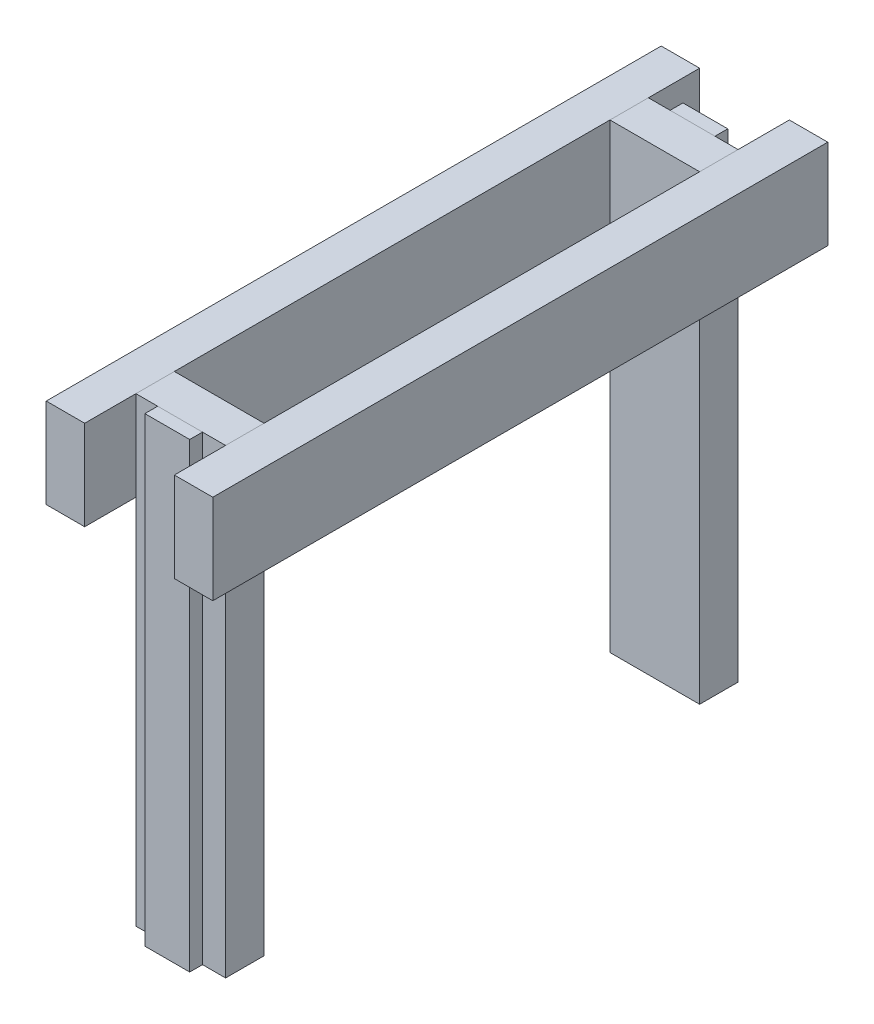
SolidWorks part; units mm, degrees
material "Oak"
ref_plane "Front Plane" through (0, 0, 0) normal (0, 0, 1) x (1, 0, 0)
ref_plane "Top Plane" through (0, 0, 0) normal (0, 1, 0) x (1, 0, 0)
ref_plane "Right Plane" through (0, 0, 0) normal (1, 0, 0) x (0, 0, -1)
sketch "Sketch3" plane through (0, 0, 0) normal (0, 1, 0) x (1, 0, 0)
  line L0 (0, 0) -> (0, -234.95) construction
  line L2 (-44.45, -254) -> (44.45, -254)
  line L3 (-44.45, -254) -> (-44.45, -215.9)
  line L4 (-44.45, -215.9) -> (44.45, -215.9)
  line L5 (44.45, -254) -> (44.45, -215.9)
  line L6 (-44.45, -254) -> (44.45, -215.9) construction
  line L7 (-44.45, -215.9) -> (44.45, -254) construction
  dimension "D1" = 38.1
  dimension "D2" = 88.9
  dimension "D3" = 254
extrude "Vertical Board" add sketch "Sketch3" against normal blind 457.2
mirror "Vertical Board Mirror" about plane through (0, 0, 0) normal (0, 0, 1) of bodies 107
sketch "Sketch6" plane through (44.45, 0, 0) normal (1, 0, 0) x (0, 0, -1)
  line L0 (-304.8, -88.9) -> (-304.8, 0)
  line L1 (-304.8, -88.9) -> (304.8, -88.9)
  line L2 (-304.8, 0) -> (304.8, 0)
  line L3 (304.8, -88.9) -> (304.8, 0)
  line L4 (-304.8, -88.9) -> (304.8, 0) construction
  line L5 (-304.8, 0) -> (304.8, -88.9) construction
  point P1 (0, -44.45)
  dimension "D1" = 88.9
  dimension "D2" = 609.6
extrude "Lateral Board" add sketch "Sketch6" along normal blind 38.1 separate body
mirror "Lateral Board Mirror" about plane through (0, 0, 0) normal (1, 0, 0) of bodies 111
sketch "Sketch7" plane through (0, 0, 254) normal (0, 0, 1) x (1, 0, 0)
  line L0 (21.5492, -457.2) -> (21.5492, 0)
  line L1 (21.5492, -457.2) -> (-22.9008, -457.2)
  line L2 (21.5492, 0) -> (-22.9008, 0)
  line L3 (-22.9008, -457.2) -> (-22.9008, 0)
  line L4 (21.5492, -457.2) -> (-22.9008, 0) construction
  line L5 (21.5492, 0) -> (-22.9008, -457.2) construction
  point P1 (-0.6758, -228.6)
  dimension "D1" = 457.2
  dimension "D2" = 44.45
extrude "Drawer Slide" add sketch "Sketch7" along normal blind 12.7 separate body
mirror "Drawer Slide Mirror" about plane through (0, 0, 0) normal (0, 0, 1) of bodies 113
